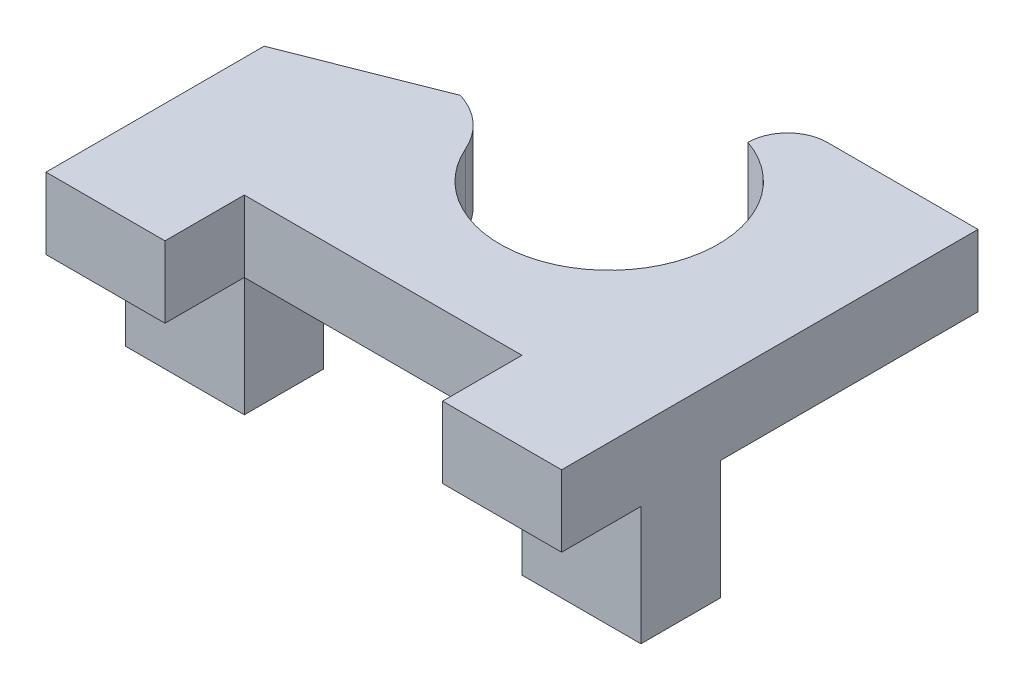
SolidWorks part; units mm, degrees
ref_plane "Front Plane" through (0, 0, 0) normal (0, 0, 1) x (1, 0, 0)
ref_plane "Top Plane" through (0, 0, 0) normal (0, 1, 0) x (1, 0, 0)
ref_plane "Right Plane" through (0, 0, 0) normal (1, 0, 0) x (0, 0, -1)
sketch "Sketch1" plane through (0, 0, 0) normal (0, 1, 0) x (1, 0, 0)
  line L0 (6.5, 2.5) -> (6.5, 0)
  line L1 (3.5, 0) -> (-3.5, 0)
  line L2 (-6.5, 0) -> (-6.5, 2.5)
  line L5 (-6.5, 2.5) -> (-6.5, 3.5)
  line L7 (6.5, 0) -> (6.5, -2)
  line L8 (6.5, -2) -> (3.5, -2)
  line L9 (3.5, 0) -> (3.5, -2)
  line L11 (-6.5, 0) -> (-6.5, -2)
  line L12 (-6.5, -2) -> (-3.5, -2)
  line L13 (-3.5, 0) -> (-3.5, -2)
  line L15 (6.5, 4.9) -> (6.5, 2.5)
  line L17 (-1.95, 4.9) -> (-2.95, 4.9)
  line L18 (-2.95, 4.9) -> (-6.5, 3.5)
  line L19 (1.7, 7.4986) -> (1.7, 8.4986)
  line L20 (1.7, 8.4986) -> (6.5, 8.4986)
  line L21 (6.5, 8.4986) -> (6.5, 4.9)
  arc A2 (-1.95, 4.9) -> (3.3581, 3.8908) centre (0.8, 4.9) ccw
  arc A3 (3.3581, 3.8908) -> (1.7, 7.4986) centre (0.8, 4.9) ccw
  point P0 (0, 0)
  dimension "D1" = 2.4
  dimension "D2" = 5.5
  dimension "D3" = 13
  dimension "D4" = 7.3
  dimension "D5" = 2.5
  dimension "D6" = 1
  dimension "D7" = 1
  dimension "D8" = 2
  dimension "D9" = 3
  dimension "D10" = 3.3
  dimension "D11" = 2.4
  dimension "D12" = 1
  dimension "D13" = 4.8
extrude "Boss-Extrude1" add sketch "Sketch1" along normal blind 1.8
fillet "Fillet1" radius 2 1 edges at (-1.95, 0.9, -4.9)
fillet "Fillet3" radius 1 1 edges at (1.7, 0.9, -8.4986)
ref_plane "Plane1" through (0, 0, 0) normal (0, -1, 0) x (-1, 0, 0)
sketch "Sketch2" plane through (0, 0, 0) normal (0, -1, 0) x (1, 0, 0)
  line L0 (6.5, 2) -> (6.5, -8.4986) construction
  line L1 (3.5, 0) -> (6.5, 0)
  line L2 (3.5, 0) -> (3.5, -2)
  line L3 (3.5, -2) -> (6.5, -2)
  line L4 (6.5, 0) -> (6.5, -2)
  line L5 (-6.5, -3.5) -> (-6.5, 2) construction
  line L6 (-3.5, 0) -> (-6.5, 0)
  line L7 (-3.5, 0) -> (-3.5, -2)
  line L8 (-3.5, -2) -> (-6.5, -2)
  line L9 (-6.5, 0) -> (-6.5, -2)
  dimension "D1" = 2
extrude "Boss-Extrude2" add sketch "Sketch2" along normal blind 3
